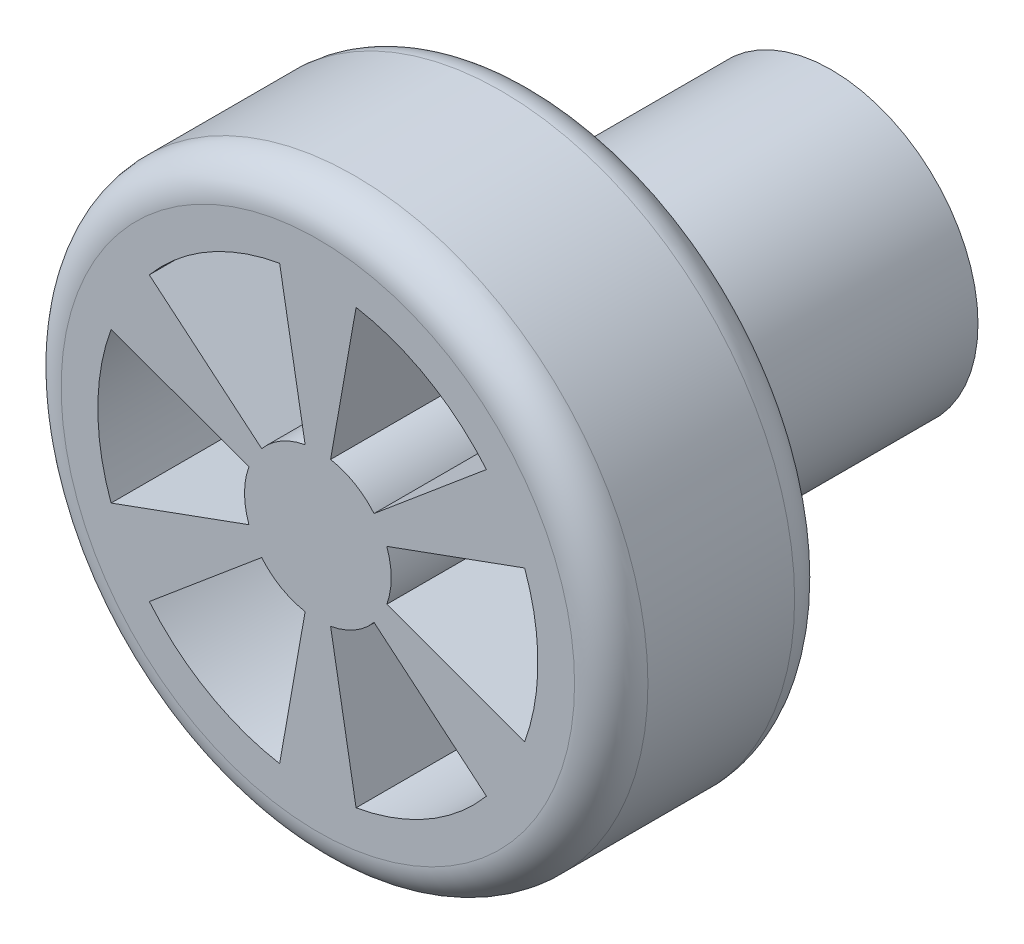
SolidWorks part; units mm, degrees
ref_plane "Front Plane" through (0, 0, 0) normal (0, 0, 1) x (1, 0, 0)
ref_plane "Top Plane" through (0, 0, 0) normal (0, 1, 0) x (1, 0, 0)
ref_plane "Right Plane" through (0, 0, 0) normal (1, 0, 0) x (0, 0, -1)
sketch "Sketch1" plane through (0, 0, 0) normal (0, 0, 1) x (1, 0, 0)
  circle A0 centre (0, 0) radius 101.6
extrude "Boss-Extrude2" add sketch "Sketch1" along normal blind 76.2
sketch "Sketch4" plane through (0, 0, 76.2) normal (0, 0, 1) x (1, 0, 0)
  circle A0 centre (0, 0) radius 25.4
  point P3 (0, 0)
sketch "Sketch5" plane through (0, 0, 0) normal (0, 0, -1) x (-1, 0, 0)
  line L0 (25.4, 0) -> (76.2, 0) construction
  line L1 (23.8682, 8.6873) -> (71.6046, 26.0619)
  line L2 (23.8682, -8.6873) -> (71.6046, -26.0619)
  line L3 (19.4575, -16.3268) -> (58.3726, -48.9804)
  line L4 (4.4107, -25.0141) -> (13.232, -75.0424)
  line L5 (-4.4107, -25.0141) -> (-13.232, -75.0424)
  line L6 (-19.4575, -16.3268) -> (-58.3726, -48.9804)
  line L7 (-23.8682, -8.6873) -> (-71.6046, -26.0619)
  line L8 (-23.8682, 8.6873) -> (-71.6046, 26.0619)
  line L9 (-19.4575, 16.3268) -> (-58.3726, 48.9804)
  line L10 (-4.4107, 25.0141) -> (-13.232, 75.0424)
  line L11 (4.4107, 25.0141) -> (13.232, 75.0424)
  line L12 (19.4575, 16.3268) -> (58.3726, 48.9804)
  arc A0 (71.6046, -26.0619) -> (71.6046, 26.0619) centre (0, 0) ccw
  arc A1 (23.8682, -8.6873) -> (23.8682, 8.6873) centre (0, 0) ccw
  arc A2 (13.232, -75.0424) -> (58.3726, -48.9804) centre (0, 0) ccw
  arc A3 (4.4107, -25.0141) -> (19.4575, -16.3268) centre (0, 0) ccw
  arc A4 (-58.3726, -48.9804) -> (-13.232, -75.0424) centre (0, 0) ccw
  arc A5 (-19.4575, -16.3268) -> (-4.4107, -25.0141) centre (0, 0) ccw
  arc A6 (-71.6046, 26.0619) -> (-71.6046, -26.0619) centre (0, 0) ccw
  arc A7 (-23.8682, 8.6873) -> (-23.8682, -8.6873) centre (0, 0) ccw
  arc A8 (-13.232, 75.0424) -> (-58.3726, 48.9804) centre (0, 0) ccw
  arc A9 (-4.4107, 25.0141) -> (-19.4575, 16.3268) centre (0, 0) ccw
  arc A10 (58.3726, 48.9804) -> (13.232, 75.0424) centre (0, 0) ccw
  arc A11 (19.4575, 16.3268) -> (4.4107, 25.0141) centre (0, 0) ccw
  point P31 (0, 0)
  dimension "D1" = 20
  dimension "D2" = 6
extrude "Cut-Extrude1" cut sketch "Sketch5" against normal up to next
fillet "Fillet1" radius 12.7 2 edges at (101.6, 0, 0) (101.6, 0, 76.2)
sketch "Sketch6" plane through (0, 0, 0) normal (0, 0, -1) x (-1, 0, 0)
  circle A0 centre (0, 0) radius 50.8
extrude "Boss-Extrude4" add sketch "Sketch6" along normal blind 101.6 separate body contours A0
